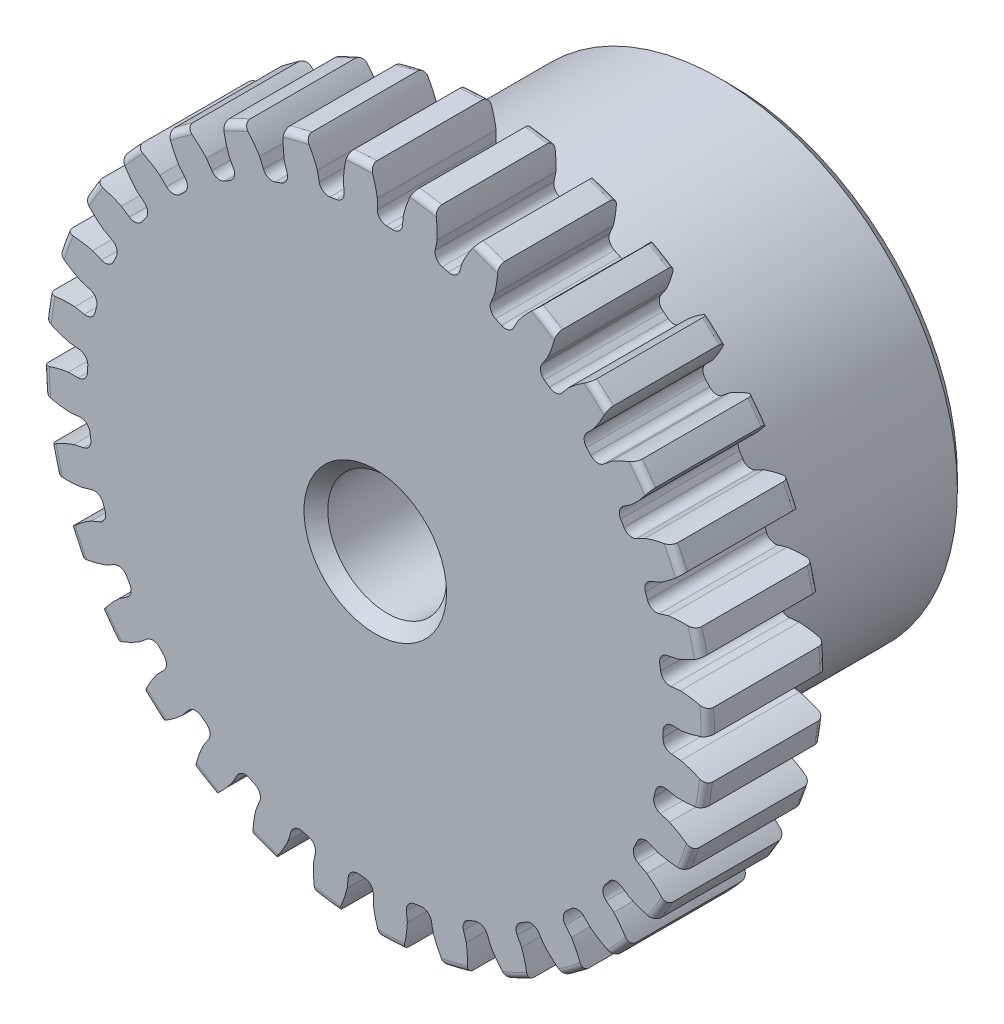
SolidWorks part; units mm, degrees
ref_plane "Front" through (0, 0, 0) normal (0, 0, 1) x (1, 0, 0)
ref_plane "Top" through (0, 0, 0) normal (0, 1, 0) x (1, 0, 0)
ref_plane "Right" through (0, 0, 0) normal (1, 0, 0) x (0, 0, -1)
sketch "Sketch1" plane through (0, 0, 0) normal (0, 0, 1) x (1, 0, 0)
  line L0 (-406.4, 0) -> (406.4, 0) construction
  circle A0 centre (0, 0) radius 8.89
  circle A1 centre (0, 0) radius 8.4709 construction
  circle A3 centre (0, 0) radius 7.6988 construction
  dimension "D1" = 1.1912
  dimension "OD" = 17.78
  dimension "Ptich Dia" = 16.9418
  dimension "Root Dia" = 15.3976
  dimension "D3" = 0.4191
  dimension "Number of Teeth" = 812.8
extrude "Boss-Extrude1" add sketch "Sketch1" against normal blind 3.175
sketch "Sketch2" plane through (0, 0, 0) normal (1, 0, 0) x (0, 0, -1)
  line L0 (3.175, 0) -> (9.525, 0)
  line L1 (3.175, 0) -> (3.175, 6.35)
  line L2 (3.175, 6.35) -> (9.525, 6.35)
  line L3 (9.525, 6.35) -> (9.525, 0)
  point P5 (9.525, -6.35)
  point P6 (0, -8.89)
  point P7 (3.175, -8.89)
  point P9 (0, 8.89)
  dimension "Face Wd" = 3.175
  dimension "B Hub Dia" = 12.7
  dimension "D O'all Lg." = 9.525
revolve "Revolve1" add sketch "Sketch2" angle 360 mid plane about L0
fillet "Fillet2" radius 0.1778 3 edges at (8.89, 0, -3.175) (8.89, 0, 0) (6.35, 0, -3.175)
sketch "Sketch3" plane through (0, 0, 0) normal (0, 0, 1) x (1, 0, 0)
  line L0 (0, 0) -> (0, 8.89) construction
  line L1 (-2.0534, 7.9399) -> (0, 8.4709)
  line L2 (-9.5921, 8.4709) -> (9.5921, 8.4709) construction
  line L3 (-9.2865, 6.0692) -> (9.2865, 10.8726) construction
  line L4 (-2.0534, 7.9399) -> (0, 0) construction
  line L5 (-5.2375, 6.3108) -> (0, 0) construction
  line L6 (-5.2375, 6.3108) -> (-0.8504, 9.9518) construction
  line L7 (-1.4318, 8.0751) -> (0, 0) construction
  line L8 (-1.4318, 8.0751) -> (0.03, 8.3343) construction
  arc A0 (-2.0534, 7.9399) -> (-5.2375, 6.3108) centre (0, 0) ccw
  circle A1 centre (0, 0) radius 8.4709 construction
  circle A2 centre (0, 0) radius 8.2011 construction
  arc A3 (-2.0534, 7.9399) -> (-1.4318, 8.0751) centre (0, 0) cw
  circle A4 centre (0, 0) radius 8.89 construction
  point P6 (0, 8.4709)
  dimension "D1" = 2.1209
  dimension "Pressure Angle" = 14.5
  dimension "D2" = 3.6056
  dimension "D3" = 5.7011
  dimension "D4" = 0.6363
  dimension "D5" = 1.4847
sketch "Sketch4" plane through (0, 0, 0) normal (0, 0, 1) x (1, 0, 0)
  line L0 (0, 0) -> (0.4151, 8.4505) construction
  line L1 (0.0531, 8.2009) -> (0.0531, 7.6986)
  line L2 (0, 8.4709) -> (0.8303, 8.4301) construction
  line L3 (0.7509, 8.1666) -> (0.7017, 7.6667)
  line L4 (0.0531, 7.6986) -> (0, 0) construction
  line L5 (0, 0) -> (0, 8.89) construction
  line L6 (-5.2375, 6.3108) -> (-0.8504, 9.9518) construction
  line L7 (-5.2375, 6.3108) -> (-0.8504, 9.9518) construction
  arc A0 (0.7017, 7.6667) -> (0.0531, 7.6986) centre (0, 0) ccw
  arc A1 (0, 8.4709) -> (0.8303, 8.4301) centre (0, 0) cw construction
  circle A2 centre (0, 0) radius 8.4709 construction
  circle A3 centre (0, 0) radius 8.2011 construction
  circle A4 centre (0, 0) radius 7.6988 construction
  arc A5 (1.8218, 9.8205) -> (-0.8504, 9.9518) centre (0, 0) ccw
  spline S0 degree 2 poles (-0.8504, 9.9518) (-0.0946, 9.1822) (0.0531, 8.2009) knots 0 0 0 1 1 1
  spline S1 degree 2 poles (1.8218, 9.8205) (0.9942, 9.1287) (0.7509, 8.1666) knots 0 0 0 1 1 1
  dimension "D1" = 0.8316
extrude "Cut-Extrude1" cut sketch "Sketch4" against normal through all
fillet "Fillet1" radius 0.2495 2 edges at (0.7017, 7.6667, -1.5875) (0.0531, 7.6986, -1.5875)
pattern_circular "CirPattern1" count 32 over 360 about axis through (0, 0, -3.175) along (0, 0, 1) of "Cut-Extrude1", "Fillet1"
sketch "Sketch5" plane through (0, 0, 0) normal (0, 0, 1) x (1, 0, 0)
  circle A0 centre (0, 0) radius 1.5875
  circle A1 centre (0, 0) radius 1.5875 construction
  dimension "Bore Min" = 3.175
  dimension "Bore Max" = 3.175
extrude "Cut-Extrude2" cut sketch "Sketch5" against normal through all
chamfer "Chamfer1" distance 0.3175 angle 45 3 edges at (6.35, 0, -9.525) (1.5875, 0, 0) (1.5875, 0, -9.525)
sketch "Pitch Dia" plane through (0, 0, 0) normal (0, 0, 1) x (1, 0, 0)
  circle A0 centre (0, 0) radius 8.4709 construction
  circle A1 centre (0, 0) radius 8.4709 construction
equation "\"D1@Boss-Extrude1\" = \"Face Wd@Sketch2\""
equation "\"D2@Sketch3\" = \"D1@Sketch3\"*1.7"
equation "\"D3@Sketch3\" = \"D1@Sketch3\"+\"D2@Sketch3\"-.001"
equation "\"D4@Sketch3\" = \"D1@Sketch3\"*.3"
equation "\"D5@Sketch3\" = \"D1@Sketch3\"-\"D4@Sketch3\""
equation "\"D1@Sketch4\" = 1.5708/(\"Number of Teeth@Sketch1\"/\"Ptich Dia@Sketch1\")"
equation "\"D1@Chamfer1\" = \"B Hub Dia@Sketch2\"*.025"
equation "\"D1@CirPattern1\" = \"Number of Teeth@Sketch1\""
equation "\"D1@Fillet1\" = \"D1@Sketch4\"*.3"
equation "\"D1@Fillet2\" = \"OD@Sketch1\"*.01"
equation "\"D1@Sketch1\" = 2.250/(\"Number of Teeth@Sketch1\"/\"Ptich Dia@Sketch1\")"
